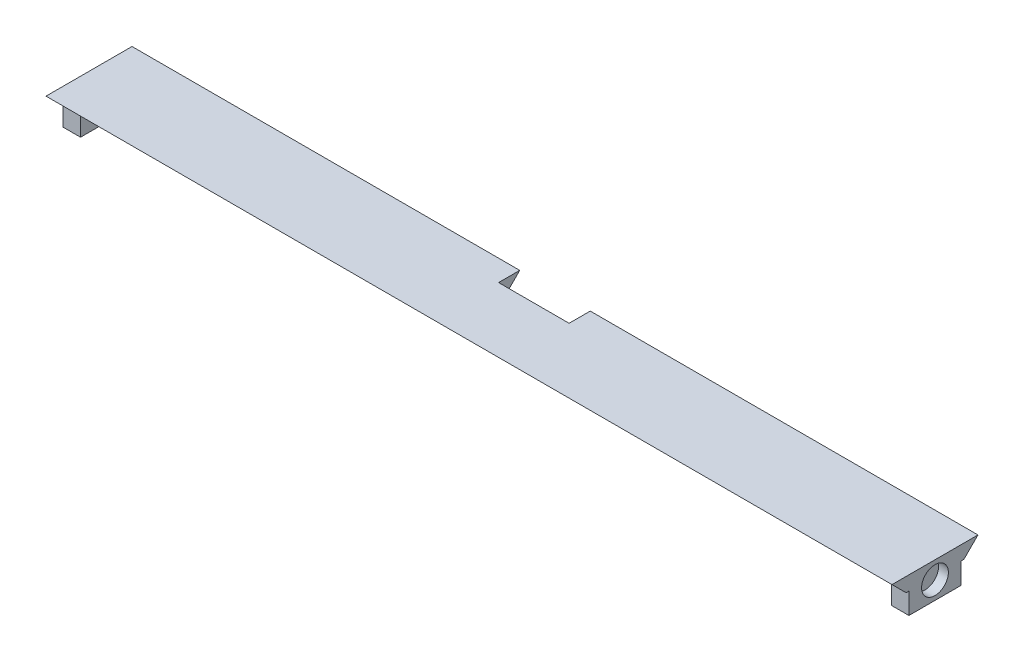
SolidWorks part; units mm, degrees
ref_plane "Plan de face" through (0, 0, 0) normal (0, 0, 1) x (1, 0, 0)
ref_plane "Plan de dessus" through (0, 0, 0) normal (0, 1, 0) x (1, 0, 0)
ref_plane "Plan de droite" through (0, 0, 0) normal (1, 0, 0) x (0, 0, -1)
sketch "Esquisse1" plane through (0, 0, 0) normal (0, 1, 0) x (1, 0, 0)
  line L1 (0, 0) -> (120, 0)
  line L2 (0, 0) -> (0, 12.2)
  line L3 (0, 12.2) -> (120, 12.2)
  line L4 (120, 0) -> (120, 12.2)
  line L5 (65, 9.2) -> (55, 9.2)
  line L6 (65, 9.2) -> (65, 12.2)
  line L7 (65, 12.2) -> (55, 12.2)
  line L8 (55, 9.2) -> (55, 12.2)
  point P9 (60, 12.2)
  point P10 (60, 12.2)
  dimension "D1" = 120
  dimension "D2" = 12.2
  dimension "D3" = 3
  dimension "D4" = 10
extrude "Boss.-Extru.2" add sketch "Esquisse1" along normal blind 2 contours L5 L8 L3 L2 L1 L4 L6 region at (60, 0, -6.0038)
sketch "Esquisse6" plane through (0, 0, 0) normal (0, -1, 0) x (1, 0, 0)
  line L0 (0, 0) -> (120, 0) construction
  line L5 (60, -9.2) -> (60, 0) construction
  line L6 (65, -9.2) -> (55, -9.2) construction
  line L11 (0, 0) -> (0, -12.2) construction
  line L12 (0, -2.4) -> (2.5, -2.4)
  line L13 (0, -2.4) -> (0, -9.8)
  line L14 (0, -9.8) -> (2.5, -9.8)
  line L15 (2.5, -2.4) -> (2.5, -9.8)
  line L16 (120, -9.8) -> (117.5, -9.8)
  line L17 (117.5, -2.4) -> (117.5, -9.8)
  line L18 (120, -2.4) -> (117.5, -2.4)
  line L19 (120, -2.4) -> (120, -9.8)
  point P17 (0, -6.1)
  point P18 (0, -6.1)
  dimension "D2" = 2.5
  dimension "D3" = 2.4
chamfer "Chanfrein2" distance 2 angle 45 4 edges at (92.5, 0, -12.2) (27.5, 0, -12.2) (60, 0, -9.2) (60, 0, 0)
extrude "Boss.-Extru.5" add sketch "Esquisse6" along normal blind 3
sketch "Esquisse9" plane through (0, 0, 0) normal (-1, 0, 0) x (0, 0, 1)
  line L0 (-2.4, -3) -> (-9.8, -3) construction
  line L1 (-12.2, 2) -> (0, 2)
  line L2 (-12.2, 2) -> (-12.2, -3)
  line L3 (-12.2, -3) -> (0, -3)
  line L4 (0, 2) -> (0, -3)
  line L5 (0, 2) -> (-12.2, -3) construction
  circle A0 centre (-6.1, -0.5) radius 1.9
  dimension "D1" = 3.8
extrude "Enlèv. mat.-Extru.5" cut sketch "Esquisse9" against normal blind 1.4 contours A0 L5 | L5 A0 region at (0, -1.2462, -5.7942) region at (0, 0.2462, -6.4058)
sketch "Esquisse10" plane through (120, 0, 0) normal (1, 0, 0) x (0, 0, -1)
  line L0 (9.8, -3) -> (2.4, -3) construction
  line L1 (0, 2) -> (12.2, 2)
  line L2 (0, 2) -> (0, -3)
  line L3 (0, -3) -> (12.2, -3)
  line L4 (12.2, 2) -> (12.2, -3)
  line L5 (0, -3) -> (12.2, 2) construction
  circle A0 centre (6.1, -0.5) radius 1.9
  dimension "D1" = 3.8
extrude "Enlèv. mat.-Extru.6" cut sketch "Esquisse10" against normal blind 1.4 contours L5 A0 | A0 L5 region at (120, -1.2462, -6.4058) region at (120, 0.2462, -5.7942)
